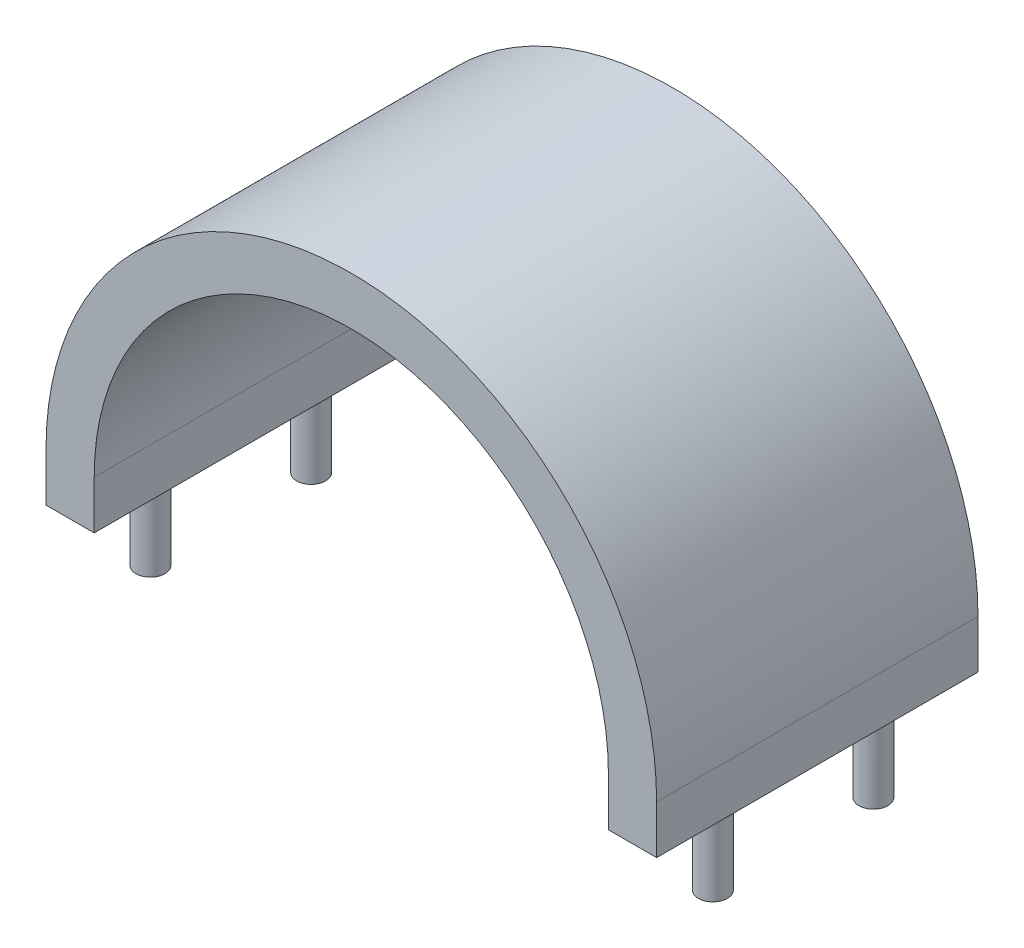
SolidWorks part; units mm, degrees
ref_plane "Front" through (0, 0, 0) normal (0, 0, 1) x (1, 0, 0)
ref_plane "Top" through (0, 0, 0) normal (0, 1, 0) x (1, 0, 0)
ref_plane "Right" through (0, 0, 0) normal (1, 0, 0) x (0, 0, -1)
sketch "草图1" plane through (0, 0, 0) normal (0, 0, 1) x (1, 0, 0)
  line L0 (0, 0) -> (0, 52.472) construction
  line L2 (-38, 14) -> (-38, 20)
  line L4 (38, 14) -> (38, 20)
  line L7 (-32, 14) -> (-32, 20)
  line L9 (32, 14) -> (32, 20)
  line L10 (-32, 14) -> (-38, 14)
  line L11 (38, 14) -> (32, 14)
  arc A0 (-38, 20) -> (38, 20) centre (0, 20) cw
  arc A1 (-32, 20) -> (32, 20) centre (0, 20) cw
  dimension "D1" = 76
  dimension "D2" = 38
  dimension "D3" = 6
  dimension "D4" = 64
  dimension "D5" = 6
extrude "凸台-拉伸1" add sketch "草图1" along normal blind 40
sketch "草图3" plane through (0, 14, 0) normal (0, -1, 0) x (1, 0, 0)
  line L0 (-35, 40) -> (-35, 0) construction
  line L1 (-38, 40) -> (-32, 40) construction
  line L2 (-38, 0) -> (-32, 0) construction
  line L3 (35, 40) -> (35, 0) construction
  line L5 (32, 40) -> (38, 40) construction
  line L6 (32, 0) -> (38, 0) construction
  circle A0 centre (-35, 30) radius 1.8
  circle A1 centre (-35, 10) radius 1.8
  circle A2 centre (35, 30) radius 1.8
  circle A3 centre (35, 10.0188) radius 1.8
extrude "凸台-拉伸2" add sketch "草图3" along normal blind 10
